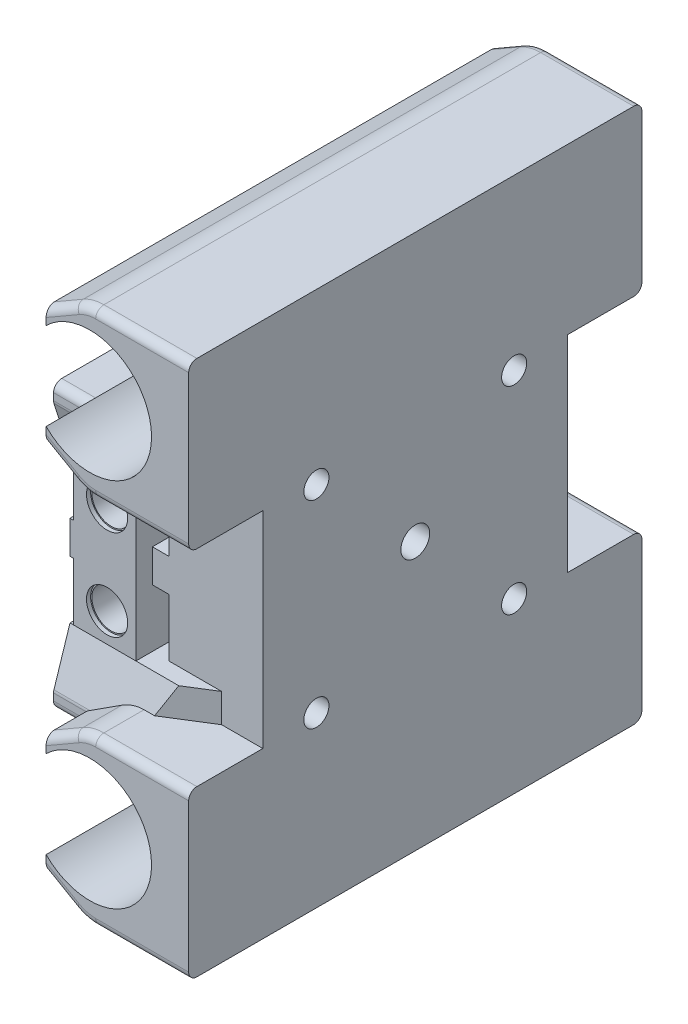
SolidWorks part; units mm, degrees
ref_plane "XY" through (0, 0, 0) normal (0, 0, 1) x (1, 0, 0)
ref_plane "XZ" through (0, 0, 0) normal (0, 1, 0) x (1, 0, 0)
ref_plane "YZ" through (0, 0, 0) normal (1, 0, 0) x (0, 0, -1)
sketch "Sketch2" plane through (0, 0, 0) normal (0, 0, 1) x (1, 0, 0)
  line L0 (-21.4, -2) -> (-20.95, -2) construction
  line L1 (0, 0) -> (-21.4, 0) construction
  line L2 (0, 0) -> (0, -22.5) construction
  line L3 (0, -32.5) -> (-12.623, -32.5)
  line L4 (-21.4, 0) -> (-21.4, -2) construction
  line L5 (-20.95, -2) -> (-20.95, -9) construction
  line L6 (-20.95, -9) -> (-21.4, -9) construction
  line L7 (-21.4, -2) -> (-21.4, -9) construction
  line L8 (-21.4, -9) -> (-21.4, -17.2) construction
  line L9 (-21.4, -17.2) -> (-17.2995, -17.2) construction
  line L10 (-17.2995, -27.8) -> (-17.2995, -29.8)
  line L11 (-17.2995, -29.8) -> (-12.623, -32.5)
  line L12 (-12.623, -32.5) -> (-21.4, -32.5) construction
  line L13 (-21.4, -17.2) -> (-21.4, -32.5) construction
  line L14 (-12, -22.5) -> (9.5178, -22.5) construction
  line L15 (0, -12.5) -> (0, -32.5)
  line L16 (0, -12.5) -> (-12.623, -12.5)
  line L17 (-17.2995, -15.2) -> (-12.623, -12.5)
  line L18 (-17.2995, -17.2) -> (-17.2995, -15.2)
  arc A0 (-17.2995, -17.2) -> (-17.2995, -27.8) centre (-12, -22.5) ccw construction
  arc A1 (-17.2995, -27.8) -> (-17.2995, -17.2) centre (-12, -22.5) ccw
  arc A2 (-4.505, -22.5) -> (-17.2995, -17.2) centre (-12, -22.5) ccw construction
  dimension "D6" = 14.99
  dimension "D1" = 32.5
  dimension "D2" = 21.4
  dimension "D3" = 0.45
  dimension "D4" = 2
  dimension "D5" = 7
  dimension "D7" = 22.5
  dimension "D8" = 12
  dimension "D9" = 17.2
  dimension "D10" = 30
  dimension "D11" = 2
extrude "Boss-Extrude1" add sketch "Sketch2" along normal blind 27.5
sketch "Sketch3" plane through (0, 0, 0) normal (0, 0, 1) x (1, 0, 0)
  line L0 (-12.623, -12.5) -> (-17.2995, -15.2) construction
  line L1 (0, -12.5) -> (-12.623, -12.5) construction
  line L2 (-12.623, -12.5) -> (-17.2995, -15.2)
  line L3 (0, -12.5) -> (-12.623, -12.5)
  line L4 (-17.2995, -15.2) -> (-17.2995, -9)
  line L5 (-17.2995, -9) -> (-11.3995, -9)
  line L6 (-11.3995, -9) -> (-11.3995, -2)
  line L7 (-11.3995, -2) -> (-17.2995, -2)
  line L8 (-17.2995, -2) -> (-17.2995, 0)
  line L9 (-17.2995, 0) -> (0, 0)
  line L10 (0, 0) -> (0, -12.5)
  dimension "D1" = 2
  dimension "D2" = 7
  dimension "D3" = 5.9
extrude "Boss-Extrude2" add sketch "Sketch3" along normal blind 18.5
sketch "Sketch4" plane through (0, 0, 0) normal (0, 0, -1) x (-1, 0, 0)
  line L0 (17.2995, -2) -> (11.3995, -2) construction
  line L1 (11.3995, -2) -> (11.3995, -9) construction
  line L2 (11.3995, -9) -> (17.2995, -9) construction
  line L3 (17.2995, -2) -> (11.3995, -2)
  line L4 (11.3995, -2) -> (11.3995, -9)
  line L5 (11.3995, -9) -> (17.2995, -9)
  line L6 (17.2995, -2) -> (17.2995, -9)
extrude "Boss-Extrude3" add sketch "Sketch4" against normal blind 2
ref_plane "Plane1" through (-21.4, 0, 0) normal (1, 0, 0) x (0, 0, -1)
sketch "Sketch5" plane through (-21.4, 0, 0) normal (1, 0, 0) x (0, 0, -1)
  line L0 (-27.5, -17.2) -> (0, -17.2) construction
  line L1 (-12.5, -17.2) -> (-22.5, -17.2)
  line L2 (-12.5, -17.2) -> (-12.5, -9)
  line L3 (-12.5, -9) -> (-20.5, -9)
  line L4 (-22.5, -17.2) -> (-22.5, -15.2)
  line L5 (-18.5, 0) -> (0, 0) construction
  line L6 (0, 0) -> (0, -17.2) construction
  line L7 (-22.5, -15.2) -> (-20.5, -9)
  line L8 (-27.5, -15.2) -> (-18.5, -15.2) construction
  line L9 (-20.5, -9) -> (-22.5, -9) construction
  line L10 (-22.5, -15.2) -> (-22.5, -9) construction
  dimension "D1" = 10
  dimension "D2" = 9
  dimension "D3" = 12.5
  dimension "D4" = 8
extrude "Boss-Extrude4" add sketch "Sketch5" along normal blind 16.4
sketch "Sketch7" plane through (-21.4, 0, 0) normal (-1, 0, 0) x (0, 0, 1)
  line L0 (18.5, 0) -> (0, 0) construction
  line L1 (20.5, -9) -> (14.5, -9)
  line L2 (20.5, -9) -> (20.5, 0)
  line L3 (20.5, 0) -> (14.5, 0)
  line L4 (14.5, -9) -> (14.5, 0)
  dimension "D1" = 6
extrude "Boss-Extrude5" add sketch "Sketch7" against normal blind 8
fillet "Fillet2" radius 5 1 edges at (-11.3995, -5.5, 2)
sketch "Sketch8" plane through (0, -9, 0) normal (0, 1, 0) x (1, 0, 0)
  line L0 (-5, -18.5) -> (-5, -23.5)
  line L1 (-5, -23.5) -> (-13, -23.5)
  line L2 (-13, -23.5) -> (-8.2, -20.5)
  line L3 (-5, -20.5) -> (-13.4, -20.5) construction
  line L4 (-5, -20.5) -> (-13.4, -20.5) construction
  line L5 (-8.2, -20.5) -> (-5, -18.5)
  dimension "D1" = 3.2
  dimension "D2" = 5
extrude "Cut-Extrude1" cut sketch "Sketch8" against normal up to surface (3.5 mm away) up to face at (-5.8743, -12.5, 22.543)
sketch "Sketch9" plane through (0, -9, 0) normal (0, 1, 0) x (1, 0, 0)
  line L0 (-21.4, -14.5) -> (-21.4, -20.5)
  line L1 (-21.4, -20.5) -> (-20.95, -20.5)
  line L2 (-13.4, -20.5) -> (-21.4, -20.5) construction
  line L3 (-20.95, -20.5) -> (-20.95, -20.2416)
  line L4 (-13.4, -14.5) -> (-21.4, -14.5) construction
  line L5 (-20.95, -14.5) -> (-21.4, -14.5)
  line L6 (-20.19, -15.5008) -> (-21.8495, -15.5008) construction
  line L7 (-20.95, -14.76) -> (-20.95, -14.5)
  line L8 (-22.9658, -16.5008) -> (-18.4164, -16.5008) construction
  line L9 (-22.6778, -18.5008) -> (-18.778, -18.5008) construction
  line L10 (-20.95, -16.76) -> (-20.95, -16.2416)
  line L11 (-20.95, -18.76) -> (-20.95, -18.2416)
  arc A0 (-20.95, -14.76) -> (-20.8189, -14.9088) centre (-20.8, -14.76) ccw
  arc A2 (-20.5068, -15.0019) -> (-20.8189, -14.9088) centre (-20.945, -15.9008) ccw
  arc A3 (-20.5068, -15.9997) -> (-20.5068, -15.0019) centre (-20.75, -15.5008) ccw
  arc A4 (-20.5068, -15.9997) -> (-20.8189, -16.0928) centre (-20.945, -15.1008) cw
  arc A5 (-20.95, -16.2416) -> (-20.8189, -16.0928) centre (-20.8, -16.2416) cw
  arc A6 (-20.95, -16.76) -> (-20.8189, -16.9088) centre (-20.8, -16.76) ccw
  arc A7 (-20.5068, -17.0019) -> (-20.8189, -16.9088) centre (-20.945, -17.9008) ccw
  arc A8 (-20.5068, -17.0019) -> (-20.5068, -17.9997) centre (-20.75, -17.5008) cw
  arc A9 (-20.5068, -17.9997) -> (-20.8189, -18.0928) centre (-20.945, -17.1008) cw
  arc A10 (-20.95, -18.2416) -> (-20.8189, -18.0928) centre (-20.8, -18.2416) cw
  arc A11 (-20.95, -18.76) -> (-20.8189, -18.9088) centre (-20.8, -18.76) ccw
  arc A12 (-20.5068, -19.0019) -> (-20.8189, -18.9088) centre (-20.945, -19.9008) ccw
  arc A13 (-20.5068, -19.9997) -> (-20.5068, -19.0019) centre (-20.75, -19.5008) ccw
  arc A14 (-20.5068, -19.9997) -> (-20.8189, -20.0928) centre (-20.945, -19.1008) cw
  arc A15 (-20.95, -20.2416) -> (-20.8189, -20.0928) centre (-20.8, -20.2416) cw
  dimension "D2" = 0.3
  dimension "D4" = 0.555
  dimension "D5" = 2
  dimension "D1" = 0.45
  dimension "D3" = 0.26
  dimension "D6" = 0.4
  dimension "D7" = 0.65
  dimension "D8" = 1
  dimension "D9" = 1
extrude "Cut-Extrude2" cut sketch "Sketch9" along normal blind 7
sketch "Sketch10" plane through (0, 0, 27.5) normal (0, 0, 1) x (1, 0, 0)
  line L0 (-17.2995, -27.8) -> (-17.2995, -17.2)
  arc A0 (-17.2995, -27.8) -> (-17.2995, -17.2) centre (-12, -22.5) ccw construction
  arc A1 (-17.2995, -27.8) -> (-17.2995, -17.2) centre (-12, -22.5) ccw
extrude "Cut-Extrude3" cut sketch "Sketch10" against normal through all
sketch "Sketch11" plane through (-17.2995, 0, 0) normal (-1, 0, 0) x (0, 0, 1)
  circle A0 centre (0, 0) radius 1.75
  dimension "D1" = 3.5
extrude "Cut-Extrude4" cut sketch "Sketch11" against normal through all
sketch "Sketch12" plane through (-21.4, 0, 0) normal (-1, 0, 0) x (0, 0, 1)
  line L0 (20.5, 0) -> (14.5, 0) construction
  circle A0 centre (17.5, -12.5) radius 2.5
  dimension "D1" = 5
  dimension "D2" = 12.5
  dimension "D3" = 17.5
extrude "Cut-Extrude5" cut sketch "Sketch12" against normal blind 0.5
sketch "Sketch13" plane through (-20.9, 0, 0) normal (-1, 0, 0) x (0, 0, 1)
  circle A0 centre (17.5, -12.5) radius 2.35
  dimension "D1" = 4.7
extrude "Cut-Extrude6" cut sketch "Sketch13" against normal offset from surface (4.5 mm away) 5 up to face at (-21.4, -12.5, 20)
sketch "Sketch14" plane through (-16.4, 0, 0) normal (-1, 0, 0) x (0, 0, 1)
  circle A0 centre (17.5, -12.5) radius 1.75
  dimension "D1" = 3.5
extrude "Cut-Extrude7" cut sketch "Sketch14" against normal blind 4
sketch "Sketch15" plane through (0, 0, 0) normal (0, 1, 0) x (1, 0, 0)
  line L0 (-20.9, -15.15) -> (-20.9, -19.85) construction
  line L1 (-20.9, -15.15) -> (-20.9, -19.85) construction
  line L2 (-20.9, -17.5) -> (-5.8804, -17.5) construction
  line L3 (-21.4, -15) -> (-19.9, -15)
  line L4 (-21.4, -20.5) -> (-21.4, -14.5) construction
  line L5 (-19.9, -15) -> (-19.9, -15.15)
  line L6 (-19.9, -15.15) -> (-15.4, -15.15)
  line L7 (-15.4, -15.15) -> (-15.4, -15.75)
  line L8 (-15.4, -15.75) -> (-13.785, -15.75)
  line L9 (-13.785, -15.75) -> (-13.785, -17.5)
  line L10 (-13.785, -17.5) -> (-21.4, -17.5)
  line L11 (-21.4, -17.5) -> (-21.4, -15)
  dimension "D1" = 1.5
  dimension "D2" = 6
  dimension "D3" = 7.615
revolve "Cut-Revolve1" cut sketch "Sketch15" angle 360 about L2
sketch "Sketch16" plane through (0, 0, 20.5) normal (0, 0, 1) x (1, 0, 0)
  line L0 (-21.4, -15.125) -> (-21.4, 15.125) construction
  line L1 (-13.4, 0) -> (-21.4, 0) construction
  circle A0 centre (-16.9, -5.5) radius 2.35
  dimension "D1" = 4.5
  dimension "D3" = 4.7
  dimension "D2" = 5.5
extrude "Cut-Extrude8" cut sketch "Sketch16" against normal up to next
sketch "Sketch17" plane through (0, 0, 20.5) normal (0, 0, 1) x (1, 0, 0)
  circle A0 centre (-16.9, -5.5) radius 2.5
  dimension "D1" = 5
extrude "Cut-Extrude9" cut sketch "Sketch17" against normal blind 0.5
fillet "Fillet3" radius 5 2 edges at (-12.623, -12.5, 24.5645) (-12.623, -32.5, 13.75)
fillet "Fillet4" radius 1 10 edges at (-15.5414, -14.1849, 27.5) (-12.5773, -12.6704, 27.5) (-15.5414, -30.8151, 27.5) (-12.5773, -32.3296, 27.5) (-19.3498, -9, 12.5) (-19.3498, -17.2, 12.5) (-19.3498, -15.2, 22.5) (-19.3498, -17.2, 22.5) (-5.6416, -12.5, 27.5) (-5.6416, -32.5, 27.5)
sketch "Sketch18" plane through (0, 0, 0) normal (1, 0, 0) x (0, 0, -1)
  line L0 (0, -32.5) -> (0, -1.75) construction
  line L1 (-18.5, 0) -> (-1.75, 0) construction
  circle A0 centre (-12, -12) radius 1.525
  dimension "D1" = 12
  dimension "D3" = 3.05
  dimension "D2" = 12
extrude "Cut-Extrude10" cut sketch "Sketch18" against normal blind 10
mirror "Mirror1" about plane through (-12, -22.5, 0) normal (0, 0, 1) of bodies 135 132
mirror "Mirror2" about plane through (-17.2995, 0, 18.5) normal (0, -1, 0) of bodies 133
